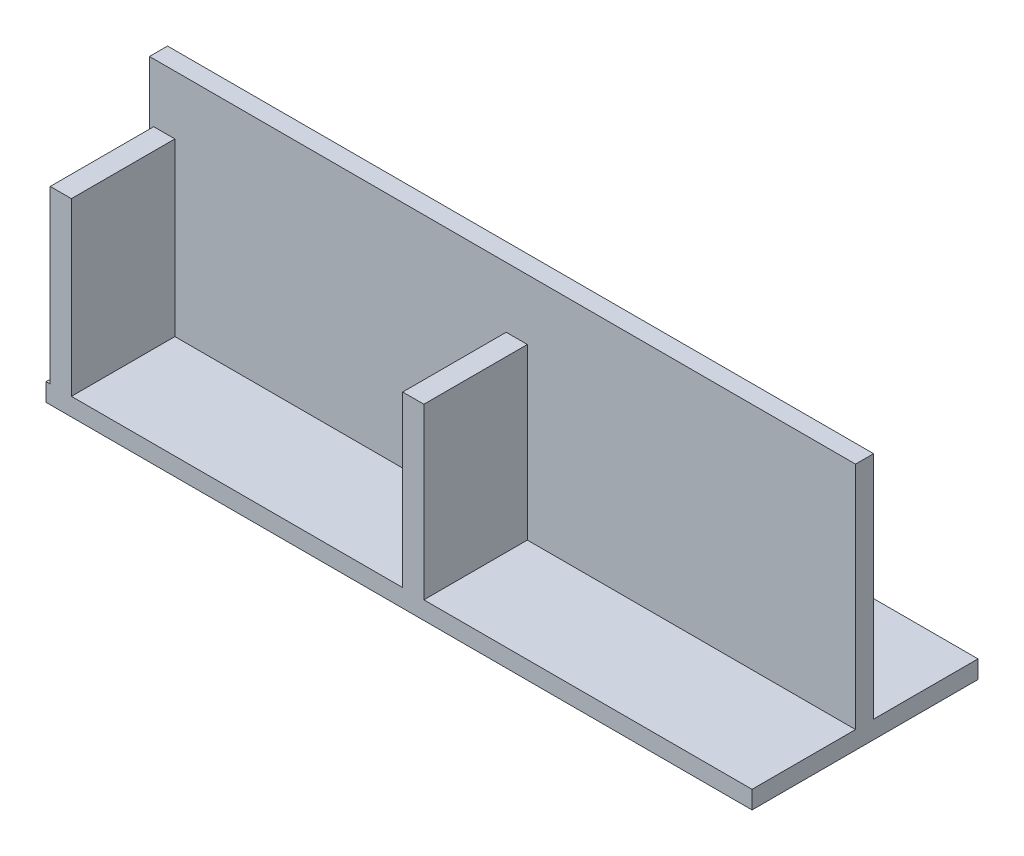
SolidWorks part; units mm, degrees
ref_plane "Front Plane" through (0, 0, 0) normal (0, 0, 1) x (1, 0, 0)
ref_plane "Top Plane" through (0, 0, 0) normal (0, 1, 0) x (1, 0, 0)
ref_plane "Right Plane" through (0, 0, 0) normal (1, 0, 0) x (0, 0, -1)
sketch "Sketch1" plane through (0, 0, 0) normal (0, 1, 0) x (1, 0, 0)
  line L1 (0, 0) -> (317.5, 0)
  line L2 (0, 0) -> (0, 101.6)
  line L3 (0, 101.6) -> (317.5, 101.6)
  line L4 (317.5, 0) -> (317.5, 101.6)
  dimension "D1" = 317.5
  dimension "D2" = 101.6
extrude "Boss-Extrude1" add sketch "Sketch1" along normal blind 8.0518
sketch "Sketch2" plane through (0, 0, 0) normal (0, 1, 0) x (1, 0, 0)
  line L0 (0, 101.6) -> (0, 0) construction
  line L1 (0, 54.6608) -> (317.5, 54.6608)
  line L2 (0, 54.6608) -> (0, 46.5328)
  line L3 (0, 46.5328) -> (317.5, 46.5328)
  line L4 (317.5, 54.6608) -> (317.5, 46.5328)
  line L5 (317.5, 0) -> (317.5, 101.6) construction
  dimension "D1" = 8.128
  dimension "D2" = 46.5328
extrude "Boss-Extrude2" add sketch "Sketch2" along normal blind 103.378 from surface starting at face at (158.75, 8.0518, -50.8)
sketch "Sketch3" plane through (0, 0, 0) normal (0, 1, 0) x (1, 0, 0)
  line L0 (0, 46.5328) -> (317.5, 46.5328) construction
  line L1 (1.905, 0) -> (11.43, 0)
  line L2 (1.905, 0) -> (1.905, 46.5328)
  line L3 (1.905, 46.5328) -> (11.43, 46.5328)
  line L4 (11.43, 0) -> (11.43, 46.5328)
  line L5 (0, 0) -> (317.5, 0) construction
  line L6 (160.401, 0) -> (169.926, 0)
  line L7 (160.401, 0) -> (160.401, 46.5328)
  line L8 (160.401, 46.5328) -> (169.926, 46.5328)
  line L9 (169.926, 0) -> (169.926, 46.5328)
  point P13 (1.3493, 0)
  dimension "D1" = 9.525
  dimension "D2" = 9.525
  dimension "D3" = 148.971
  dimension "D4" = 1.905
extrude "Boss-Extrude3" add sketch "Sketch3" along normal blind 76.9874 from surface contours L1 L4 L3 L2 starting at face at (158.75, 8.0518, -23.2664)
extrude "Boss-Extrude4" add sketch "Sketch3<3>" along normal blind 76.1746 from surface contours L9 L8 L7 L6 starting at face at (164.465, 8.0518, -23.2664)
sketch "Sketch3<3>" plane through (0, 0, 0) normal (0, 1, 0) x (1, 0, 0) same geometry as "Sketch3"
equation "\"length\"=12.5"
equation "\"D1@Sketch1\"=\"length\""
equation "\"width\"=4"
equation "\"D2@Sketch1\"=\"width\""
